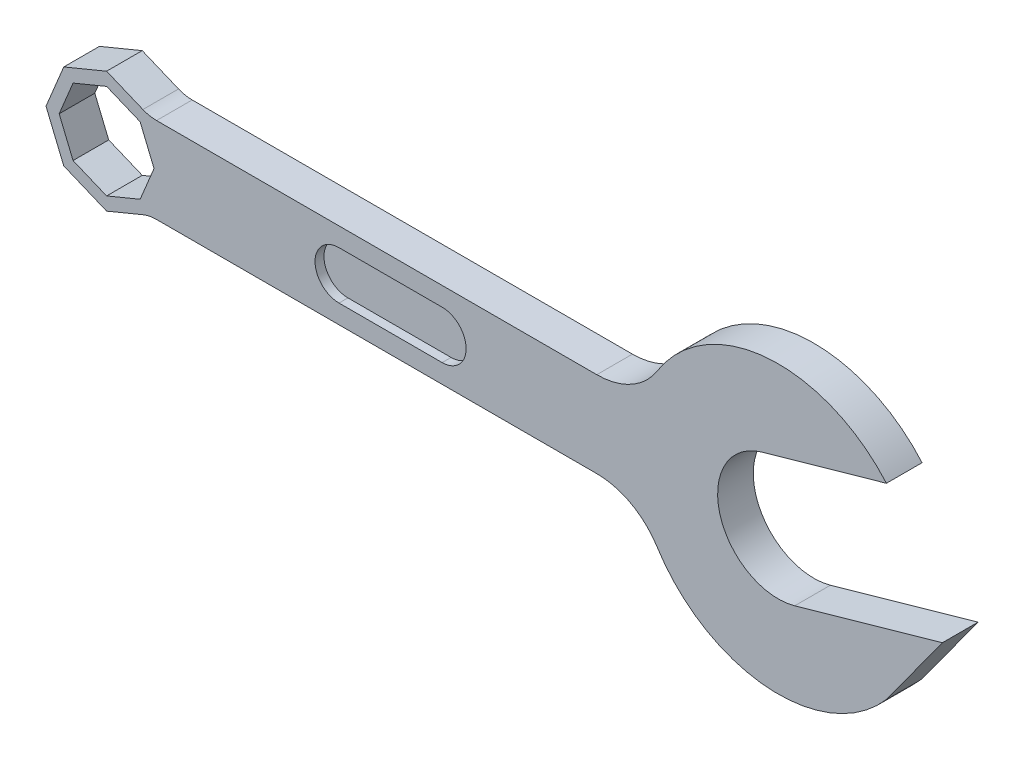
SolidWorks part; units mm, degrees
ref_plane "Front Plane" through (0, 0, 0) normal (0, 0, 1) x (1, 0, 0)
ref_plane "Top Plane" through (0, 0, 0) normal (0, 1, 0) x (1, 0, 0)
ref_plane "Right Plane" through (0, 0, 0) normal (1, 0, 0) x (0, 0, -1)
sketch "Sketch1" plane through (0, 0, 0) normal (0, 0, 1) x (1, 0, 0)
  line L0 (-893.4013, 0) -> (43776.6641, 0) construction
  line L1 (0, -893.4013) -> (0, 43776.6641) construction
  line L2 (0, -913.2632) -> (0, 43756.8023) construction
  line L3 (-61.6221, 0) -> (-32.6948, 0) construction
  line L4 (91.9406, 26.2624) -> (56.9584, 16.3569)
  line L5 (-126.8242, 17) -> (-138.8451, 12.0208)
  line L6 (-138.8451, 12.0208) -> (-143.8242, 0)
  line L7 (-143.8242, 0) -> (-138.8451, -12.0208)
  line L8 (-138.8451, -12.0208) -> (-126.8242, -17)
  line L9 (-126.8242, -17) -> (-116.6411, -12.782)
  line L10 (-114.8034, -12.0208) -> (-109.8242, 0)
  line L11 (-109.8242, 0) -> (-114.8034, 12.0208)
  line L12 (-116.6411, 12.782) -> (-126.8242, 17)
  line L13 (66.2215, -16.3569) -> (107.6308, -4.6316)
  line L14 (-112.8143, 12.0208) -> (10.6883, 12.0208)
  line L15 (-112.8143, -12.0208) -> (10.6883, -12.0208)
  line L16 (91.9406, -26.2624) -> (107.6308, -4.6316)
  line L17 (-61.6221, 6.7282) -> (-32.6948, 6.7282)
  line L18 (-61.6221, -6.7282) -> (-32.6948, -6.7282)
  arc A0 (91.9406, 26.2624) -> (27.6172, 21.3713) centre (61.5899, 0) ccw
  circle A1 centre (-126.8242, 0) radius 17 construction
  arc A2 (56.9584, 16.3569) -> (66.2215, -16.3569) centre (61.5899, 0) ccw
  arc A3 (10.6883, 12.0208) -> (27.6172, 21.3713) centre (10.6883, 32.0208) ccw
  arc A4 (91.9406, -26.2624) -> (27.6172, -21.3713) centre (61.5899, 0) cw
  arc A5 (10.6883, -12.0208) -> (27.6172, -21.3713) centre (10.6883, -32.0208) cw
  arc A6 (27.6172, 21.3713) -> (27.6172, -21.3713) centre (61.5899, 0) ccw
  arc A7 (-61.6221, 6.7282) -> (-61.6221, -6.7282) centre (-61.6221, 0) ccw
  arc A8 (-32.6948, -6.7282) -> (-32.6948, 6.7282) centre (-32.6948, 0) ccw
  arc A9 (-116.6411, -12.782) -> (-112.8143, -12.0208) centre (-112.8143, -22.0208) cw
  arc A10 (-116.6411, 12.782) -> (-112.8143, 12.0208) centre (-112.8143, 22.0208) ccw
  point P32 (-47.1585, 0)
  point P37 (0, 0)
  dimension "D2" = 34
  dimension "D3" = 20
  dimension "D4" = 10
  dimension "D5" = 10
  dimension "D1" = 34
extrude "Boss-Extrude1" add sketch "Sketch1" along normal mid plane 10 contours A10 L12 L5 L6 L7 L8 L9 A9 L15 A5 A6 A3 L14 A8 L18 A7 L17 | A0 A6 A4 L16 L13 A2 L4 region at (74.1286, 22.4428, 0) region at (19.6873, 0, 0)
extrude "Boss-Extrude2" add sketch "Sketch1<3>" along normal mid plane 5 contours L18 A8 L17 A7 region at (-47.1585, 0, 0)
sketch "Sketch1<3>" plane through (0, 0, 0) normal (0, 0, 1) x (1, 0, 0) same geometry as "Sketch1"
sketch "Sketch2" plane through (0, 0, 5) normal (0, 0, 1) x (1, 0, 0)
  line L1 (-126.8242, 13.307) -> (-136.2337, 9.4095)
  line L2 (-136.2337, 9.4095) -> (-140.1312, 0)
  line L3 (-140.1312, 0) -> (-136.2337, -9.4095)
  line L4 (-136.2337, -9.4095) -> (-126.8242, -13.307)
  line L5 (-126.8242, -13.307) -> (-117.4148, -9.4095)
  line L6 (-117.4148, -9.4095) -> (-113.5173, 0)
  line L7 (-113.5173, 0) -> (-117.4148, 9.4095)
  line L8 (-117.4148, 9.4095) -> (-126.8242, 13.307)
  circle A0 centre (-126.8242, 0) radius 12.294 construction
  dimension "D1" = 28
extrude "Cut-Extrude1" cut sketch "Sketch2" against normal through all both and the other way through all
